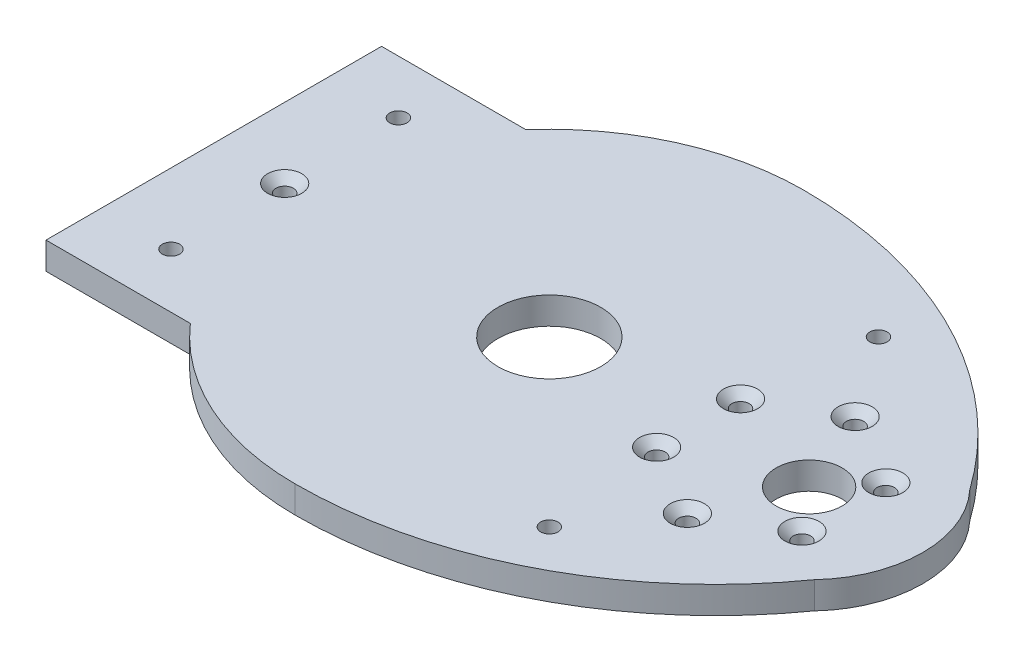
SolidWorks part; units mm, degrees
ref_plane "Front Plane" through (0, 0, 0) normal (0, 0, 1) x (1, 0, 0)
ref_plane "Top Plane" through (0, 0, 0) normal (0, 1, 0) x (1, 0, 0)
ref_plane "Right Plane" through (0, 0, 0) normal (1, 0, 0) x (0, 0, -1)
sketch "Sketch1" plane through (0, 0, 0) normal (0, 1, 0) x (1, 0, 0)
  line L2 (68, -47) -> (0, -47)
  line L4 (-62, 31) -> (-62, -31)
  line L5 (-62, 31) -> (-35.327, 31)
  line L6 (-62, -31) -> (-35.327, -31)
  circle A0 centre (0, 0) radius 37 construction
  circle A1 centre (0, 0) radius 47
  circle A2 centre (48, 0) radius 6.1
  circle A3 centre (0, 0) radius 9.5
  circle A4 centre (0, 0) radius 47 construction
  arc A6 (-35.327, 31) -> (-35.327, -31) centre (0, 0) cw
  circle A7 centre (48, 0) radius 18.5 construction
  arc A8 (0, 47) -> (63.3152, 14.3682) centre (0, -30.7409) cw
  arc A9 (0, -47) -> (63.3152, -14.3682) centre (0, 30.7409) ccw
  arc A10 (63.3152, -14.3682) -> (63.3152, 14.3682) centre (48, 0) ccw
  circle A11 centre (48, 0) radius 21 construction
  point P17 (-62, 0)
  dimension "D1" = 74
  dimension "D3" = 12.2
  dimension "D6" = 19
  dimension "D10" = 57
  dimension "D9" = 37
  dimension "D11" = 57
  dimension "D4" = 48
  dimension "D7" = 62
  dimension "D8" = 62
  dimension "D2" = 10
  dimension "D12" = 2.5
extrude "Boss-Extrude1" add sketch "Sketch1" along normal blind 5 contours A2 A1 | A1 L5 L4 L6 | A9 A10 A8 A1 A2 region at (-52.3528, 0, 0) region at (-18.8434, 0, -41.605) region at (35.0806, 0, -37.3257)
sketch "Sketch2" plane through (0, 5, 0) normal (0, 1, 0) x (1, 0, 0)
  circle A0 centre (41, 0) radius 15.5 construction
  circle A1 centre (48, 0) radius 6.1 construction
  circle A2 centre (48, 0) radius 6.1 construction
  circle A3 centre (41, -15.5) radius 1.6
  circle A4 centre (27.5766, -7.75) radius 1.6
  circle A5 centre (27.5766, 7.75) radius 1.6
  circle A6 centre (41, 15.5) radius 1.6
  circle A7 centre (54.4234, 7.75) radius 1.6
  circle A8 centre (54.4234, -7.75) radius 1.6
  point P20 (41, 0)
  dimension "D1" = 31
  dimension "D3" = 3.2
  dimension "D2" = 7
  dimension "D4" = 6
hole_wizard "CSK for M3 Countersunk Flat Head Screw1" positions "Sketch3" profile "Sketch4" countersink size "M3" standard "ISO"
sketch "Sketch3" plane through (0, 5, 0) normal (0, 1, 0) x (1, 0, 0)
  point P0 (27.5766, 7.75)
  point P3 (41, 15.5)
  point P6 (27.5766, -7.75)
  point P9 (41, -15.5)
  point P12 (54.4234, -7.75)
  point P15 (54.4234, 7.75)
sketch "Sketch4" plane through (27.5766, 5, -7.75) normal (1, 0, 0) x (0, 0, 1)
  line L0 (0, 0) -> (0, 10.4614)
  line L1 (0, 10.4614) -> (1.6, 9.5)
  line L2 (1.6, 9.5) -> (1.6, 1.55)
  line L3 (1.6, 1.55) -> (3.15, 0)
  line L5 (3.15, 0) -> (0, 0)
  line L6 (-1.6, 1.55) -> (-3.15, 0) construction
  line L10 (0, 10.4614) -> (-1.6, 9.5) construction
  line L11 (0, -6.35) -> (0, 107.95) construction
  dimension "Hole Dia." = 3.2
  dimension "Hole Depth" = 9.5
  dimension "Near C'Sink Dia." = 6.3
  dimension "Near C'Sink Angle" = 90
  dimension "Drill Angle" = 118
sketch "Sketch5" plane through (0, 5, 0) normal (0, 1, 0) x (1, 0, 0)
  circle A0 centre (0, 0) radius 37 construction
  dimension "D1" = 74
sketch "Sketch10" plane through (0, 0, 0) normal (0, -1, 0) x (1, 0, 0)
  line L0 (0, 0) -> (0, 43) construction
  line L1 (0, 0) -> (30.4056, 30.4056) construction
  circle A0 centre (0, 0) radius 37 construction
  circle A1 centre (0, 0) radius 37 construction
  circle A2 centre (-49, 0) radius 14 construction
  circle A3 centre (0, 0) radius 43 construction
  circle A4 centre (30.4056, 30.4056) radius 1.25
  dimension "D1" = 49
  dimension "D2" = 28
  dimension "D4" = 2.5
  dimension "D3" = 86
  dimension "D5" = 45
hole_wizard "CSK for M3 Countersunk Flat Head Screw2" positions "Sketch11" profile "Sketch12" countersink size "M3" standard "ISO" end condition through all
sketch "Sketch11" plane through (0, 0, 0) normal (0, -1, 0) x (-1, 0, 0)
  circle A0 centre (0, 0) radius 43 construction
  point P0 (-30.4056, -30.4056)
  point P7 (-30.4056, 30.4056)
sketch "Sketch12" plane through (30.4056, 0, 30.4056) normal (1, 0, 0) x (0, 0, -1)
  line L0 (0, 0) -> (0, 5)
  line L1 (0, 5) -> (1.6, 5)
  line L2 (1.6, 5) -> (1.6, 1.55)
  line L3 (1.6, 1.55) -> (3.15, 0)
  line L5 (3.15, 0) -> (0, 0)
  line L6 (-1.6, 1.55) -> (-3.15, 0) construction
  line L11 (0, -6.35) -> (0, 107.95) construction
  dimension "Thru Hole Dia." = 3.2
  dimension "Thru Hole Depth" = 5
  dimension "Near C'Sink Dia." = 6.3
  dimension "Near C'Sink Angle" = 90
sketch "Sketch6" plane through (0, 0, 0) normal (0, -1, 0) x (1, 0, 0)
  circle A0 centre (-49, -21.11) radius 1.6
  circle A1 centre (-49, 20.91) radius 1.6
  circle A2 centre (-49, -0.1) radius 1.6
  circle A3 centre (-49, 0) radius 14 construction
  circle A4 centre (-49, 0) radius 14 construction
  dimension "D1" = 3.2
  dimension "D2" = 3.2
  dimension "D4" = 21.11
  dimension "D5" = 42.02
  dimension "D6" = 21.01
extrude "Cut-Extrude2" cut sketch "Sketch6" against normal through all
hole_wizard "CSK for M3 Countersunk Flat Head Screw3" positions "Sketch13" profile "Sketch14" countersink size "M3" standard "ISO" end condition through all
sketch "Sketch13" plane through (0, 5, 0) normal (0, 1, 0) x (1, 0, 0)
  point P0 (-49, 0.1)
sketch "Sketch14" plane through (-49, 5, -0.1) normal (1, 0, 0) x (0, 0, 1)
  line L0 (0, 0) -> (0, 5)
  line L1 (0, 5) -> (1.6, 5)
  line L2 (1.6, 5) -> (1.6, 1.55)
  line L3 (1.6, 1.55) -> (3.15, 0)
  line L5 (3.15, 0) -> (0, 0)
  line L6 (-1.6, 1.55) -> (-3.15, 0) construction
  line L11 (0, -6.35) -> (0, 107.95) construction
  dimension "Thru Hole Dia." = 3.2
  dimension "Thru Hole Depth" = 5
  dimension "Near C'Sink Dia." = 6.3
  dimension "Near C'Sink Angle" = 90
equation "\"D6@Sketch6\"=\"D5@Sketch6\"/2"
